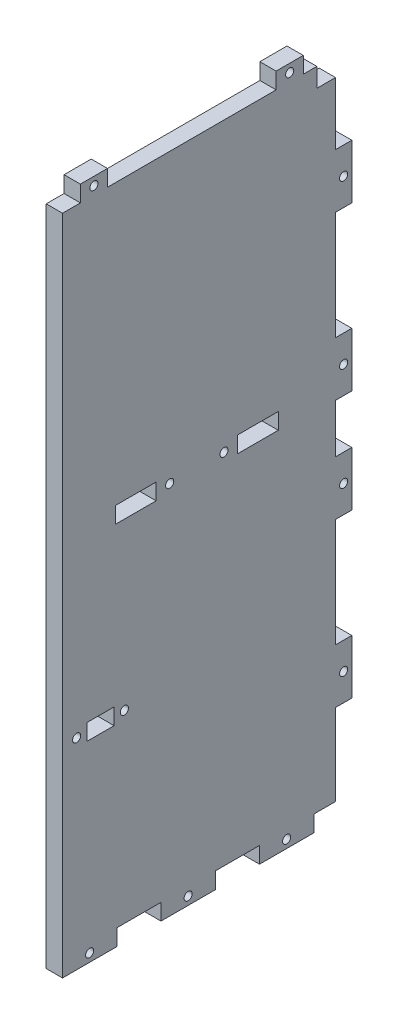
SolidWorks part; units mm, degrees
ref_plane "Plan de face" through (0, 0, 0) normal (0, 0, 1) x (1, 0, 0)
ref_plane "Plan de dessus" through (0, 0, 0) normal (0, 1, 0) x (1, 0, 0)
ref_plane "Plan de droite" through (0, 0, 0) normal (1, 0, 0) x (0, 0, -1)
sketch "Esquisse1" plane through (0, 0, 0) normal (1, 0, 0) x (0, 0, -1)
  line L0 (97.1531, 0) -> (-102.2664, 0) construction
  line L1 (-50.29, 119) -> (50.29, 119)
  line L2 (-50.29, 119) -> (-50.29, -119)
  line L3 (-50.29, -119) -> (50.29, -119)
  line L4 (50.29, 119) -> (50.29, -119)
  line L5 (0, 172.7153) -> (0, -236.1933) construction
  line L7 (-41.29, -48) -> (-31.29, -48)
  line L8 (-41.29, -48) -> (-41.29, -54)
  line L9 (-41.29, -54) -> (-31.29, -54)
  line L10 (-31.29, -48) -> (-31.29, -54)
  line L15 (-30.795, 16) -> (-15.795, 16)
  line L16 (-30.795, 16) -> (-30.795, 10)
  line L17 (-30.795, 10) -> (-15.795, 10)
  line L18 (-15.795, 16) -> (-15.795, 10)
  line L19 (14.205, 16) -> (29.205, 16)
  line L20 (14.205, 16) -> (14.205, 10)
  line L21 (14.205, 10) -> (29.205, 10)
  line L22 (29.205, 16) -> (29.205, 10)
  dimension "D1" = 238
  dimension "D2" = 100.58
  dimension "D4" = 119
  dimension "D13" = 15
  dimension "D14" = 15
  dimension "D15" = 30
  dimension "D16" = 6
  dimension "D17" = 6
  dimension "D3" = 50.29
  dimension "D5" = 103
  dimension "D6" = 19.495
  dimension "D7" = 9
  dimension "D8" = 167
  dimension "D9" = 6
  dimension "D10" = 10
extrude "Boss.-Extru.1" add sketch "Esquisse1" along normal blind 6
sketch "Esquisse3" plane through (6, 0, 0) normal (1, 0, 0) x (0, 0, -1)
  line L0 (-50.29, -119) -> (50.29, -119) construction
  line L1 (-50.29, -119) -> (-30.29, -119)
  line L2 (-50.29, -119) -> (-50.29, -125)
  line L3 (-50.29, -125) -> (-30.29, -125)
  line L4 (-30.29, -119) -> (-30.29, -125)
  line L5 (245.3741, 0) -> (-166.5298, 0) construction
  line L6 (50.29, -119) -> (50.29, 119) construction
  line L7 (22.29, -119) -> (42.29, -119)
  line L8 (22.29, -119) -> (22.29, -125)
  line L9 (22.29, -125) -> (42.29, -125)
  line L10 (0, 208.6671) -> (0, -232.3841) construction
  line L11 (-50.29, -119) -> (50.29, -119) construction
  line L12 (42.29, -119) -> (42.29, -125)
  line L13 (56.29, 29) -> (56.29, 9)
  line L14 (50.29, 9) -> (56.29, 9)
  line L15 (50.29, 29) -> (50.29, 9)
  line L16 (50.29, 29) -> (56.29, 29)
  line L17 (56.29, 89) -> (56.29, 69)
  line L18 (50.29, 69) -> (56.29, 69)
  line L19 (50.29, 89) -> (50.29, 69)
  line L20 (50.29, 89) -> (56.29, 89)
  line L21 (50.29, 119) -> (-50.29, 119) construction
  line L22 (50.29, -89) -> (56.29, -89)
  line L23 (50.29, -89) -> (50.29, -69)
  line L24 (50.29, -69) -> (56.29, -69)
  line L25 (56.29, -89) -> (56.29, -69)
  line L26 (50.29, -29) -> (56.29, -29)
  line L27 (50.29, -29) -> (50.29, -9)
  line L28 (50.29, -9) -> (56.29, -9)
  line L29 (0, -208.6671) -> (0, 232.3841) construction
  line L30 (-14, -119) -> (6, -119)
  line L31 (-14, -119) -> (-14, -125)
  line L32 (-14, -125) -> (6, -125)
  line L33 (6, -119) -> (6, -125)
  line L34 (50.29, -119) -> (50.29, 119) construction
  line L35 (56.29, -29) -> (56.29, -9)
  line L36 (38.41, 119) -> (28.41, 119)
  line L37 (38.41, 119) -> (38.41, 125)
  line L38 (38.41, 125) -> (28.41, 125)
  line L39 (28.41, 119) -> (28.41, 125)
  line L40 (-50.29, 119) -> (-50.29, -119) construction
  line L41 (-33.71, 119) -> (-43.71, 119)
  line L42 (-33.71, 119) -> (-33.71, 125)
  line L43 (-33.71, 125) -> (-43.71, 125)
  line L44 (-43.71, 119) -> (-43.71, 125)
  dimension "D2" = 20
  dimension "D3" = 6
  dimension "D4" = 20
  dimension "D5" = 8
  dimension "D6" = 6
  dimension "D7" = 6
  dimension "D8" = 20
  dimension "D9" = 6
  dimension "D10" = 20
  dimension "D11" = 6
  dimension "D12" = 20
  dimension "D13" = 16.29
  dimension "D14" = 30
  dimension "D15" = 40
  dimension "D16" = 6
  dimension "D17" = 10
  dimension "D18" = 11.88
  dimension "D19" = 6.58
  dimension "D20" = 10
  dimension "D21" = 6
  dimension "D22" = 16.29
extrude "Boss.-Extru.5" add sketch "Esquisse3" against normal blind 6
sketch "Esquisse7" plane through (0, 0, 0) normal (-1, 0, 0) x (0, 0, 1)
  line L1 (-50.29, 119) -> (-43.41, 119)
  line L2 (-50.29, 119) -> (-50.29, 112)
  line L3 (-50.29, 112) -> (-43.41, 112)
  line L4 (-43.41, 119) -> (-43.41, 112)
  dimension "D1" = 7
  dimension "D2" = 6.88
extrude "Enlèv. mat.-Extru.3" cut sketch "Esquisse7" against normal blind 6
sketch "Esquisse8" plane through (0, 0, 0) normal (-1, 0, 0) x (0, 0, 1)
  line L0 (-51.0214, 13) -> (44.3386, 13) construction
  line L1 (50.29, -125) -> (30.29, -125) construction
  line L2 (-14.205, 16) -> (-14.205, 10) construction
  line L3 (15.795, 10) -> (15.795, 16) construction
  line L4 (14, -119) -> (14, -125) construction
  line L5 (60.5401, -51) -> (10.4957, -51) construction
  line L6 (41.29, -48) -> (41.29, -54) construction
  line L7 (31.29, -54) -> (31.29, -48) construction
  line L8 (41.29, -54) -> (31.29, -54) construction
  line L9 (53.2872, 122) -> (-67.0711, 122) construction
  line L10 (33.71, 125) -> (43.71, 125) construction
  line L11 (-28.41, 125) -> (-28.41, 119) construction
  line L12 (33.71, 119) -> (33.71, 125) construction
  line L13 (-67.0711, -122) -> (72.8873, -122) construction
  line L14 (15.795, 16) -> (30.795, 16) construction
  line L16 (-22.29, -119) -> (-22.29, -125) construction
  line L17 (30.29, -125) -> (30.29, -119) construction
  line L18 (-53.29, 135.0788) -> (-53.29, -173.0788) construction
  line L19 (-56.29, 69) -> (-56.29, 89) construction
  line L21 (-56.29, -69) -> (-50.29, -69) construction
  line L22 (-50.29, 9) -> (-56.29, 9) construction
  line L23 (-56.29, 89) -> (-50.29, 89) construction
  circle A0 centre (4, -122) radius 1.5
  circle A1 centre (-9.205, 13) radius 1.5
  circle A2 centre (10.795, 13) radius 1.5
  circle A4 centre (27.5, -51) radius 1.5
  circle A5 centre (45.08, -51) radius 1.5
  circle A6 centre (38.71, 122) radius 1.5
  circle A7 centre (-33.41, 122) radius 1.5
  circle A8 centre (40.29, -122) radius 1.5
  circle A9 centre (-53.29, 79) radius 1.5
  circle A10 centre (-32.29, -122) radius 1.5
  circle A11 centre (-53.29, 19) radius 1.5
  circle A12 centre (-53.29, -79) radius 1.5
  circle A13 centre (-53.29, -19) radius 1.5
  dimension "D1" = 3
  dimension "D2" = 3
  dimension "D4" = 3
  dimension "D5" = 3
  dimension "D6" = 5
  dimension "D7" = 5
  dimension "D8" = 10
  dimension "D9" = 3
  dimension "D10" = 3
  dimension "D15" = 3
  dimension "D16" = 3
  dimension "D17" = 5
  dimension "D18" = 5
  dimension "D20" = 3
  dimension "D21" = 3
  dimension "D22" = 3
  dimension "D23" = 3
  dimension "D24" = 10
  dimension "D25" = 10
  dimension "D26" = 3
  dimension "D27" = 3
  dimension "D28" = 3
  dimension "D29" = 10
  dimension "D31" = 10
  dimension "D32" = 10
  dimension "D11" = 3.79
  dimension "D12" = 3.79
  dimension "D13" = 3
  dimension "D14" = 3
  dimension "D19" = 3
  dimension "D30" = 10
extrude "Enlèv. mat.-Extru.4" cut sketch "Esquisse8" against normal blind 6
equation "\"D3@Esquisse1\"=\"D2@Esquisse1\"/2"
equation "\"D4@Esquisse1\"=\"D1@Esquisse1\"/2"
